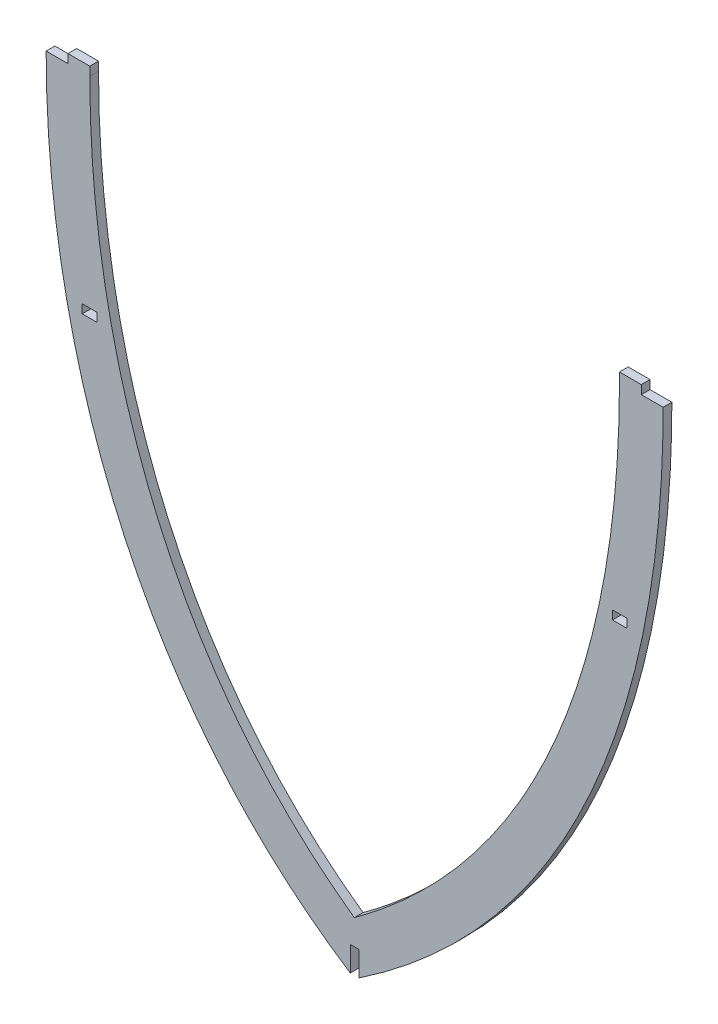
SolidWorks part; units mm, degrees
material "birch 3mm plywood"
ref_plane "Front" through (0, 0, 0) normal (0, 0, 1) x (1, 0, 0)
ref_plane "Top" through (0, 0, 0) normal (0, 1, 0) x (1, 0, 0)
ref_plane "Right" through (0, 0, 0) normal (1, 0, 0) x (0, 0, -1)
sketch "Sketch1" plane through (0, 0, 0) normal (0, 0, 1) x (1, 0, 0)
  line L0 (88.6, -155) -> (88.6, -152) construction
  line L1 (93.6, -155) -> (93.6, -152) construction
  line L2 (98.6, -152) -> (93.6, -152) construction
  line L8 (-88.6, -152) -> (-93.6, -152)
  line L9 (-93.6, -152) -> (-93.6, -155)
  line L10 (-93.6, -155) -> (-88.6, -155)
  line L11 (-88.6, -155) -> (-88.6, -152)
  line L12 (93.6, -152) -> (88.6, -152)
  line L13 (88.6, -152) -> (88.6, -155)
  line L14 (88.6, -155) -> (93.6, -155)
  line L15 (93.6, -155) -> (93.6, -152)
  line L16 (-106, -83) -> (-98.5, -83)
  line L17 (-106, -83) -> (-68.5834, -83) construction
  line L18 (-98.5, -83) -> (-98.5, -80)
  line L19 (-68.5834, -80) -> (-106, -80) construction
  line L20 (-98.5, -80) -> (-91, -80)
  line L21 (-91, -80) -> (-91, -83)
  line L22 (106, -83) -> (98.5, -83)
  line L23 (68.5834, -83) -> (106, -83) construction
  line L24 (98.5, -83) -> (98.5, -80)
  line L25 (106, -80) -> (68.5834, -80) construction
  line L26 (98.5, -80) -> (91, -80)
  line L27 (91, -80) -> (91, -83)
  spline S0 degree 3 poles (-606.6311, -2686.1966) (-1331.3466, 4216.9715) (2505.2437, -3263.0373) (-2575.6318, 1120.6224) knots -6.031856 -6.031856 -6.031856 -6.031856 4.281025 4.281025 4.281025 4.281025 only from (106, -83) to (0, -306.0893) construction
  spline S1 degree 3 poles (689.6249, -2848.8726) (504.5633, 3901.714) (-1758.8386, -3459.7843) (2297.6608, 1523.3776) knots -4.72173 -4.72173 -4.72173 -4.72173 4.086582 4.086582 4.086582 4.086582 only from (-106, -83) to (0, -306.0893) construction
  spline S2 degree 3 poles (106, -83) (106, -174.4433) (74.7629, -256.783) (0, -306.0893) knots 0 0 0 0 1 1 1 1
  spline S3 degree 3 poles (-106, -83) (-106, -171.1717) (-74.7629, -258.4392) (0, -306.0893) knots 0 0 0 0 1 1 1 1
  spline S4 degree 1 poles (-91, -83) (-0.1167, -287.9264) knots 0 0 1 1 construction
  spline S5 degree 1 poles (91, -83) (-0.1167, -287.9264) knots 0 0 1 1 construction
  spline S6 degree 3 poles (-91, -83) (-91, -88.0686) (-90.7842, -98.2205) (-89.4717, -118.3778) (-86.1468, -143.2308) (-79.3681, -172.0711) (-69.7174, -199.532) (-57.1183, -225.2317) (-44.0961, -244.8889) (-32.112, -259.4019) (-22.3248, -269.6427) (-13.4811, -277.6134) (-5.9927, -283.6258) (-2.0894, -286.5211) (-0.1167, -287.9264) knots 0 0 0 0 0.059983 0.119967 0.239934 0.359901 0.479868 0.599835 0.719802 0.779785 0.839769 0.899752 0.929744 0.959735 0.959735 0.959735 0.959735
  spline S7 degree 3 poles (-0.1167, -287.9264) (1.8708, -286.4802) (5.8114, -283.5064) (13.356, -277.3846) (22.2576, -269.3453) (32.0901, -259.1217) (44.1097, -244.7411) (57.1396, -225.4116) (69.7252, -200.2046) (79.363, -173.1605) (85.0093, -149.2619) (88.136, -129.4393) (89.7964, -114.2526) (90.6189, -101.351) (90.9458, -90.91) (91, -85.632) (91, -83) knots 0 0 0 0 0.030008 0.060016 0.120032 0.180048 0.240064 0.360096 0.480129 0.600161 0.720193 0.780209 0.840225 0.900241 0.930249 0.960257 0.960257 0.960257 0.960257
  point P28 (-93.6, -152)
  point P29 (0, 0)
  point P30 (-88.6, -155)
  point P32 (-88.6, -152)
  point P33 (88.6, -152)
  point P35 (88.6, -155)
  point P40 (93.6, -155)
  point P41 (93.6, -152)
  dimension "D2" = 7.5
  dimension "D3" = 7.5
  dimension "D1" = 15
extrude "Boss-Extrude1" add sketch "Sketch1" along normal mid plane 3
sketch "Sketch2" plane through (0, 0, 1.5) normal (0, 0, 1) x (1, 0, 0)
  line L0 (-1.5, -296.5952) -> (1.5, -296.5952)
  line L1 (1.5, -296.5952) -> (1.5, -306.0893)
  line L2 (1.5, -306.0893) -> (-1.5, -306.0893)
  line L3 (1.5, -306.0893) -> (-1.5, -306.0893) construction
  line L4 (-1.5, -83) -> (-1.5, -306.0893) construction
  line L5 (-1.5, -306.0893) -> (-1.5, -296.5952)
extrude "Cut-Extrude1" cut sketch "Sketch2" against normal blind 3
